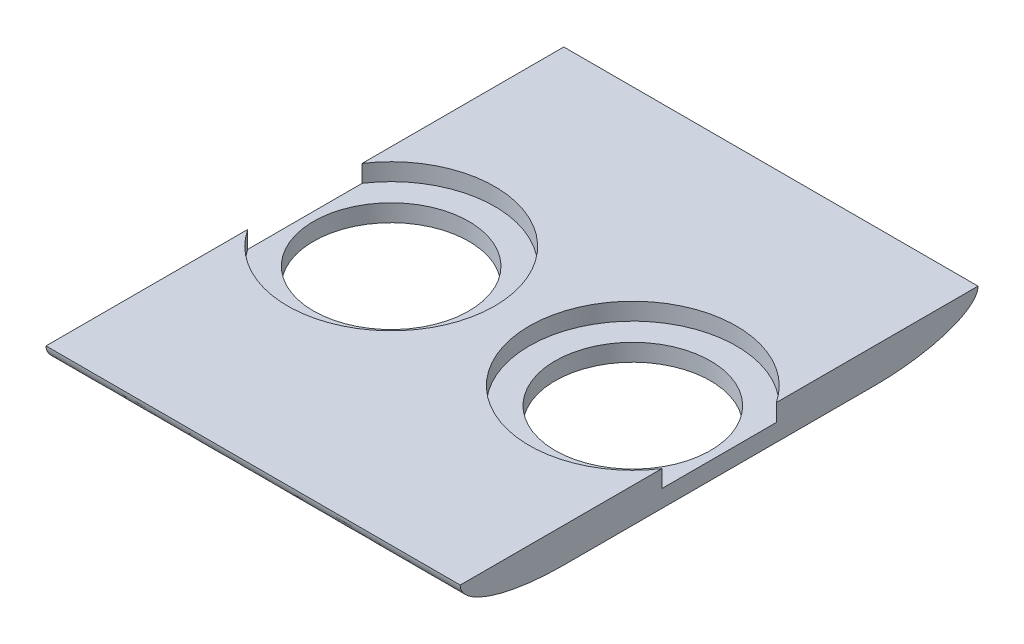
SolidWorks part; units mm, degrees
ref_plane "Ön Düzlem" through (0, 0, 0) normal (0, 0, 1) x (1, 0, 0)
ref_plane "Üst Düzlem" through (0, 0, 0) normal (0, 1, 0) x (1, 0, 0)
ref_plane "Sağ Düzlem" through (0, 0, 0) normal (1, 0, 0) x (0, 0, -1)
sketch "Sketch2" plane through (0, 0, 0) normal (0, 1, 0) x (1, 0, 0)
  line L1 (-60, -75) -> (60, -75)
  line L2 (-60, -75) -> (-60, 75)
  line L3 (-60, 75) -> (60, 75)
  line L4 (60, -75) -> (60, 75)
  line L5 (-60, -75) -> (60, 75) construction
  line L6 (-60, 75) -> (60, -75) construction
  point P0 (0, 0)
  dimension "D1" = 120
  dimension "D2" = 150
extrude "Boss-Extrude1" add sketch "Sketch2" along normal blind 10
sketch "Sketch3" plane through (0, 10, 0) normal (0, 1, 0) x (1, 0, 0)
  line L0 (60, -75) -> (60, 75) construction
  line L1 (-60, 75) -> (-60, -75) construction
  line L2 (60, 75) -> (-60, 75) construction
  circle A0 centre (35, 0) radius 30
  circle A1 centre (-35, 0) radius 30
  dimension "D1" = 60
  dimension "D2" = 60
  dimension "D4" = 25
  dimension "D3" = 25
  dimension "D5" = 75
  dimension "D6" = 75
extrude "Cut-Extrude1" cut sketch "Sketch3" against normal blind 5
sketch "Sketch4" plane through (0, 5, 0) normal (0, 1, 0) x (1, 0, 0)
  circle A0 centre (-35, 0) radius 22.5
  circle A1 centre (35, 0) radius 22.5
  dimension "D1" = 45
  dimension "D2" = 45
extrude "Cut-Extrude2" cut sketch "Sketch4" against normal blind 5
fillet "Fillet1" radius 30 2 edges at (0, 0, -75) (0, 0, 75) second distance 10 first distance on face at (-35, 0, 22.5)
